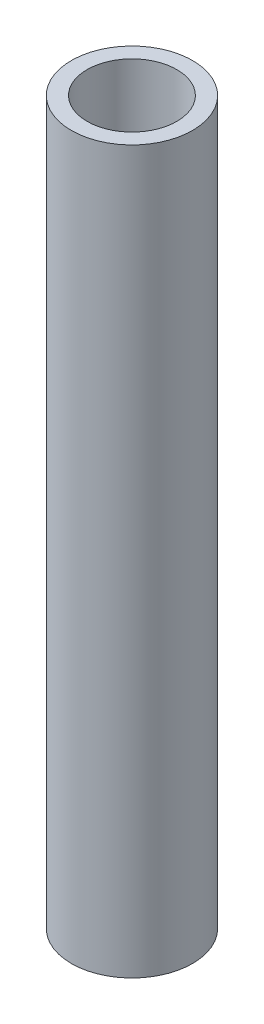
SolidWorks part; units mm, degrees
ref_plane "Front Plane" through (0, 0, 0) normal (0, 0, 1) x (1, 0, 0)
ref_plane "Top Plane" through (0, 0, 0) normal (0, 1, 0) x (1, 0, 0)
ref_plane "Right Plane" through (0, 0, 0) normal (1, 0, 0) x (0, 0, -1)
sketch "Sketch1" plane through (0, 0, 0) normal (0, 1, 0) x (1, 0, 0)
  circle A0 centre (0, 0) radius 10.668
  circle A1 centre (0, 0) radius 7.8994
  dimension "D1" = 21.336
  dimension "D2" = 15.7988
extrude "Boss-Extrude1" add sketch "Sketch1" along normal blind 127
